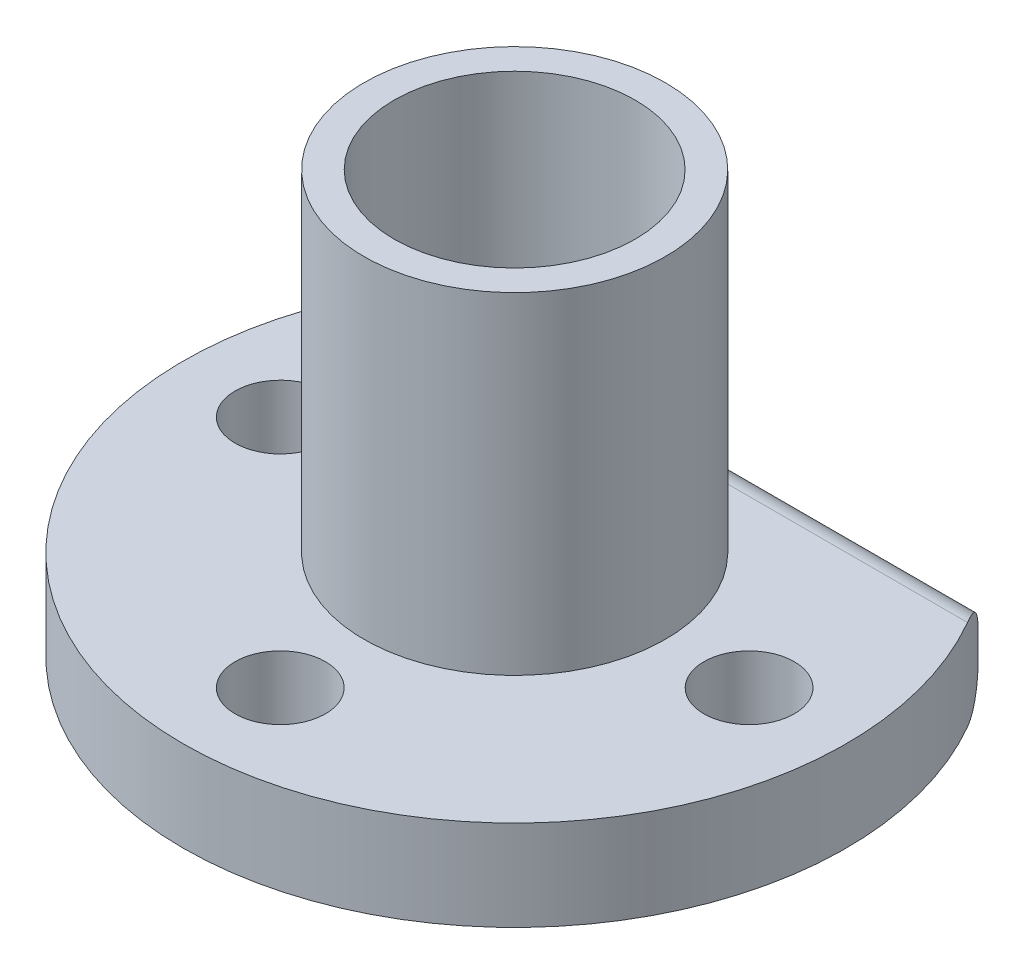
SolidWorks part; units mm, degrees
ref_plane "Front" through (0, 0, 0) normal (0, 0, 1) x (1, 0, 0)
ref_plane "Top" through (0, 0, 0) normal (0, 1, 0) x (1, 0, 0)
ref_plane "Right" through (0, 0, 0) normal (1, 0, 0) x (0, 0, -1)
sketch "Esquisse1" plane through (0, 0, 0) normal (0, 0, 1) x (1, 0, 0)
  line L0 (0, 0) -> (0, 18.0588) construction
  line L1 (4, 0) -> (4, 15)
  line L2 (4, 15) -> (5, 15)
  line L3 (5, 15) -> (5, 4)
  line L4 (5, 4) -> (11, 4)
  line L5 (11, 4) -> (11, 1)
  line L6 (11, 1) -> (5, 1)
  line L7 (5, 1) -> (5, 0)
  line L8 (5, 0) -> (4, 0)
  dimension "D1" = 8
  dimension "D2" = 10
  dimension "D3" = 22
  dimension "D4" = 1
  dimension "D5" = 15
  dimension "D6" = 3
revolve "Révolution1" add sketch "Esquisse1" angle 360 about L0
sketch "Esquisse2" plane through (0, 1, 0) normal (0, -1, 0) x (1, 0, 0)
  line L0 (0, 0) -> (7.7782, 0) construction
  circle A0 centre (7.7782, 0) radius 1.5
  circle A1 centre (0, -7.7782) radius 1.5
  circle A2 centre (-7.7782, 0) radius 1.5
  circle A3 centre (0, 7.7782) radius 1.5
  point P13 (0, 0)
  dimension "D1" = 3
  dimension "D3" = 11
  dimension "D2" = 4
extrude "Enlèv. mat.-Extru.1" cut sketch "Esquisse2" against normal through all
sketch "Esquisse3" plane through (0, 4, 0) normal (0, 1, 0) x (1, 0, 0)
  line L0 (8.8741, 6.5) -> (-8.8741, 6.5)
  line L1 (8.8741, 6.5) -> (8.8741, 14.2745)
  line L2 (8.8741, 14.2745) -> (-8.8741, 14.2745)
  line L3 (-8.8741, 14.2745) -> (-8.8741, 6.5)
  circle A0 centre (0, 0) radius 11 construction
  dimension "D1" = 6.5
extrude "Enlèv. mat.-Extru.2" cut sketch "Esquisse3" against normal through all
fillet "Congé1" radius 1 2 edges at (-4.8296, 1, -6.5) (-4.8296, 4, -6.5)
